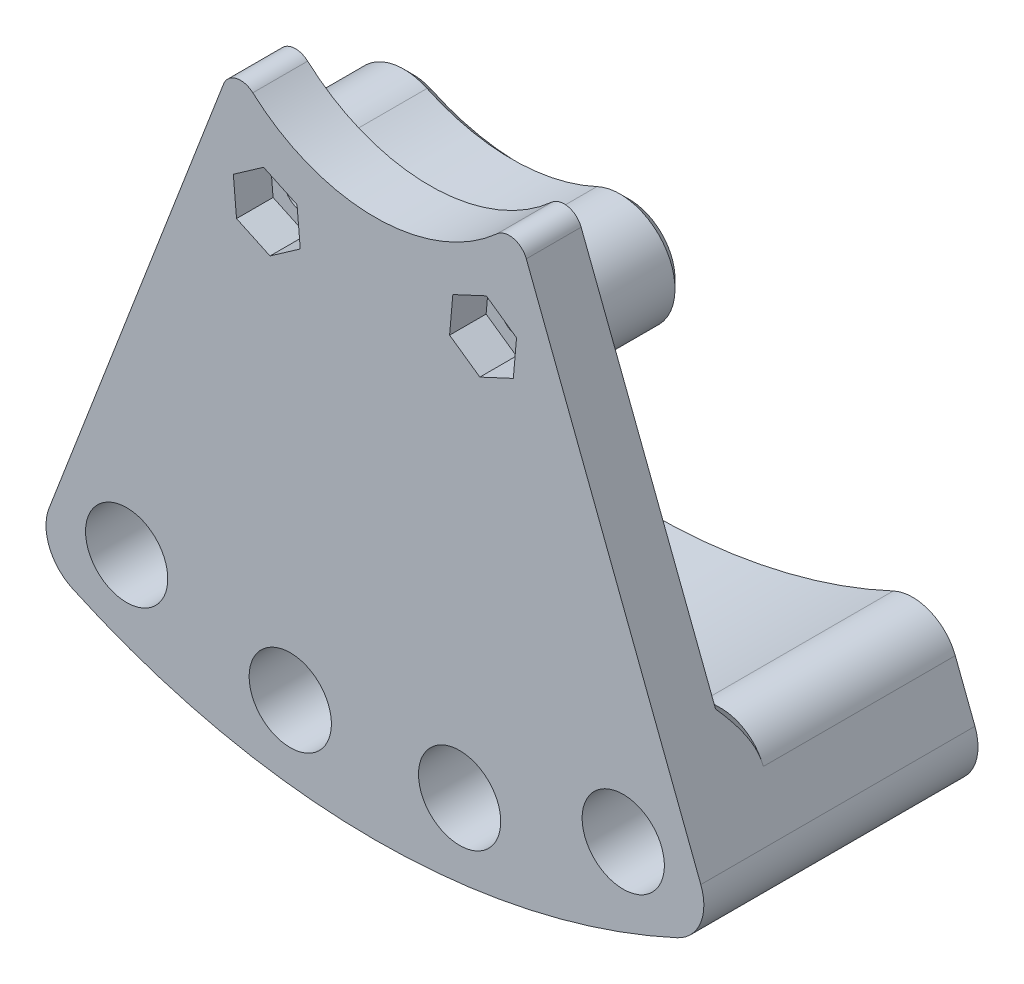
SolidWorks part; units mm, degrees
ref_plane "Front Plane" through (0, 0, 0) normal (0, 0, 1) x (1, 0, 0)
ref_plane "Top Plane" through (0, 0, 0) normal (0, 1, 0) x (1, 0, 0)
ref_plane "Right Plane" through (0, 0, 0) normal (1, 0, 0) x (0, 0, -1)
sketch "Sketch1" plane through (0, 0, 0) normal (0, 0, 1) x (1, 0, 0)
  line L0 (-27.1705, -65.5954) -> (-9.2674, -70.3926) construction
  line L1 (-9.2674, -70.3926) -> (9.2674, -70.3926) construction
  line L2 (9.2674, -70.3926) -> (27.1705, -65.5954) construction
  line L3 (27.1705, -65.5954) -> (0, 0) construction
  line L4 (0, 0) -> (9.2674, -70.3926) construction
  line L5 (0, 0) -> (-9.2674, -70.3926) construction
  line L6 (0, 0) -> (-27.1705, -65.5954) construction
  line L7 (0, 0) -> (0, -70.3926) construction
  line L8 (-31.5, -54.5596) -> (-39.5, -68.416)
  line L9 (31.5, -54.5596) -> (39.5, -68.416)
  line L10 (-31.5, -54.5596) -> (0, 0) construction
  line L11 (0, 0) -> (31.5, -54.5596) construction
  circle A0 centre (0, 0) radius 71 construction
  circle A1 centre (-27.1705, -65.5954) radius 2.15
  circle A2 centre (-9.2674, -70.3926) radius 2.15
  circle A3 centre (9.2674, -70.3926) radius 2.15
  circle A4 centre (27.1705, -65.5954) radius 2.15
  arc A5 (-39.5, -68.416) -> (39.5, -68.416) centre (0, 0) ccw
  arc A6 (-31.5, -54.5596) -> (31.5, -54.5596) centre (0, 0) ccw
  point P17 (35.5, -61.4878)
  point P19 (0, -63)
  dimension "D1" = 142
  dimension "D5" = 4.3
  dimension "D2" = 15
  dimension "D3" = 15
  dimension "D4" = 15
  dimension "D6" = 16
  dimension "D7" = 60
extrude "Boss-Extrude1" add sketch "Sketch1" along normal blind 24
sketch "Sketch2" plane through (0, 0, 24) normal (0, 0, 1) x (1, 0, 0)
  line L0 (-31.5, -54.5596) -> (-15.4375, -12.7154)
  line L1 (15.4375, -12.7154) -> (31.5, -54.5596)
  line L2 (31.5, -54.5596) -> (39.5, -68.416)
  line L3 (-39.5, -68.416) -> (-31.5, -54.5596)
  line L4 (15.4375, -12.7154) -> (-15.4375, -12.7154) construction
  line L5 (0, 0) -> (0, -12.7154) construction
  arc A1 (39.5, -68.416) -> (-39.5, -68.416) centre (0, 0) cw
  arc A2 (-15.4375, -12.7154) -> (15.4375, -12.7154) centre (0, 0) ccw
  dimension "D2" = 20
  dimension "D1" = 42
extrude "Boss-Extrude2" add sketch "Sketch2" along normal blind 6
fillet "Fillet1" radius 2 2 edges at (15.4375, -12.7154, 27) (-15.4375, -12.7154, 27)
sketch "Sketch3" plane through (0, 0, 30) normal (0, 0, 1) x (1, 0, 0)
  line L0 (-31.5, -54.5596) -> (-37.2907, -69.6448)
  line L1 (-39.5, -68.416) -> (-31.5, -54.5596)
  line L2 (-16.5652, -15.653) -> (-31.5, -54.5596) construction
  arc A0 (-39.5, -68.416) -> (39.5, -68.416) centre (0, 0) ccw construction
  arc A1 (-37.2907, -69.6448) -> (-39.5, -68.416) centre (-34.0691, -61.2524) cw
extrude "Cut-Extrude1" cut sketch "Sketch3" against normal through all
mirror "Mirror1" about plane through (0, 0, 0) normal (1, 0, 0) of "Cut-Extrude1"
fillet "Fillet2" radius 5 4 edges at (37.2907, -69.6448, 15) (-37.2907, -69.6448, 15) (-31.5, -54.5596, 12) (31.5, -54.5596, 12)
chamfer "Chamfer1" distance 3 angle 45 3 edges at (30.7089, -56.944, 24) (-30.7089, -56.944, 24) (0, -63, 24)
sketch "Sketch4" plane through (0, 0, 0) normal (0, 0, -1) x (-1, 0, 0)
  circle A0 centre (-27.1705, -65.5954) radius 4.5
  circle A1 centre (-9.2674, -70.3926) radius 4.5
  circle A2 centre (9.2674, -70.3926) radius 4.5
  circle A3 centre (27.1705, -65.5954) radius 4.5
  dimension "D1" = 9
extrude "Cut-Extrude2" cut sketch "Sketch4" against normal through all from offset 10 offset against normal yes
sketch "Sketch5" plane through (0, 0, 24) normal (0, 0, -1) x (-1, 0, 0)
  line L0 (0, 0) -> (-11.8333, -25.3766) construction
  line L1 (-11.8333, -25.3766) -> (11.8333, -25.3766) construction
  line L2 (11.8333, -25.3766) -> (0, 0) construction
  line L3 (0, 0) -> (0, -25.3766) construction
  circle A0 centre (0, 0) radius 28 construction
  circle A1 centre (-11.8333, -25.3766) radius 2.15
  circle A2 centre (11.8333, -25.3766) radius 2.15
  dimension "D1" = 56
  dimension "D2" = 4.3
  dimension "D3" = 50
extrude "Cut-Extrude3" cut sketch "Sketch5" against normal through all
sketch "Sketch6" plane through (0, 0, 30) normal (0, 0, 1) x (1, 0, 0)
  line L0 (0, -22) -> (0, -34) construction
  circle A0 centre (0, 0) radius 28 construction
  arc A1 (-9.2976, -19.9388) -> (-14.369, -30.8145) centre (-11.8333, -25.3766) ccw
  arc A2 (9.2976, -19.9388) -> (14.369, -30.8145) centre (11.8333, -25.3766) cw
  arc A3 (-14.369, -30.8145) -> (14.369, -30.8145) centre (0, 0) ccw
  arc A4 (-9.2976, -19.9388) -> (9.2976, -19.9388) centre (0, 0) ccw
  circle A5 centre (-11.8333, -25.3766) radius 2.15
  circle A6 centre (11.8333, -25.3766) radius 2.15
  circle A7 centre (11.8333, -25.3766) radius 2.15 construction
  circle A8 centre (-11.8333, -25.3766) radius 2.15 construction
  point P3 (-11.8333, -25.3766)
  point P4 (11.8333, -25.3766)
  dimension "D1" = 12
extrude "Boss-Extrude3" add sketch "Sketch6" against normal blind 16
chamfer "Chamfer2" distance 1 angle 45 4 edges at (-17.2712, -22.8409, 14) (0, -34, 14) (0, -22, 14) (17.2712, -22.8409, 14)
sketch "Sketch7" plane through (0, 0, 30) normal (0, 0, 1) x (1, 0, 0)
  line L1 (-8.5227, -23.0585) -> (-12.1855, -21.3505)
  line L2 (-12.1855, -21.3505) -> (-15.4961, -23.6686)
  line L3 (-15.4961, -23.6686) -> (-15.1439, -27.6947)
  line L4 (-15.1439, -27.6947) -> (-11.4811, -29.4027)
  line L5 (-11.4811, -29.4027) -> (-8.1705, -27.0846)
  line L6 (-8.1705, -27.0846) -> (-8.5227, -23.0585)
  line L7 (8.5227, -23.0585) -> (8.1705, -27.0846)
  line L8 (8.1705, -27.0846) -> (11.4811, -29.4027)
  line L9 (11.4811, -29.4027) -> (15.1439, -27.6947)
  line L10 (15.1439, -27.6947) -> (15.4961, -23.6686)
  line L11 (15.4961, -23.6686) -> (12.1855, -21.3505)
  line L12 (12.1855, -21.3505) -> (8.5227, -23.0585)
  circle A0 centre (-11.8333, -25.3766) radius 3.5 construction
  circle A1 centre (11.8333, -25.3766) radius 3.5 construction
  circle A2 centre (0, 0) radius 24.5832 construction
  dimension "D1" = 7
extrude "Cut-Extrude4" cut sketch "Sketch7" against normal blind 4
chamfer "Chamfer3" distance 1 angle 45 4 edges at (-17.2712, -22.8409, 24) (0, -34, 24) (0, -22, 24) (17.2712, -22.8409, 24)
